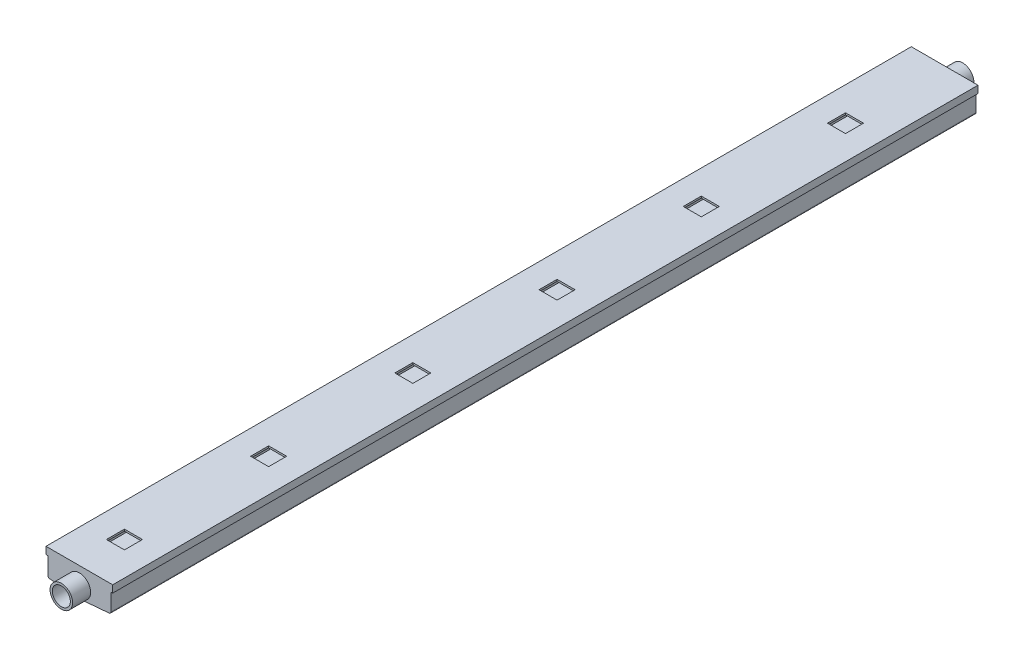
SolidWorks part; units mm, degrees
ref_plane "Front Plane" through (0, 0, 0) normal (0, 0, 1) x (1, 0, 0)
ref_plane "Top Plane" through (0, 0, 0) normal (0, 1, 0) x (1, 0, 0)
ref_plane "Right Plane" through (0, 0, 0) normal (1, 0, 0) x (0, 0, -1)
sketch "Sketch1" plane through (0, 0, 0) normal (0, 0, 1) x (1, 0, 0)
  line L2 (0, 0) -> (0, 34.29)
  line L3 (0, 34.29) -> (88.9, 34.29)
  line L4 (88.9, 0) -> (88.9, 34.29)
  line L5 (0, 0) -> (44.45, -3.81)
  line L6 (44.45, -3.81) -> (88.9, 0)
  point P5 (44.45, 34.29)
  dimension "D1" = 34.29
  dimension "D2" = 88.9
  dimension "D3" = 38.1
extrude "Boss-Extrude1" add sketch "Sketch1" along normal blind 1219.2
sketch "Sketch2" plane through (88.9, 0, 0) normal (1, 0, 0) x (0, 0, -1)
  line L0 (0, 0) -> (0, 34.29) construction
  line L1 (-1219.2, 34.29) -> (0, 34.29)
  line L2 (-1219.2, 34.29) -> (-1219.2, 26.67)
  line L3 (-1219.2, 26.67) -> (0, 26.67)
  line L4 (0, 34.29) -> (0, 26.67)
  dimension "D1" = 7.62
extrude "Boss-Extrude2" add sketch "Sketch2" along normal blind 2.54
sketch "Sketch3" plane through (0, 0, 0) normal (-1, 0, 0) x (0, 0, 1)
  line L0 (1219.2, 34.29) -> (1219.2, 0) construction
  line L1 (0, 34.29) -> (1219.2, 34.29)
  line L2 (0, 34.29) -> (0, 26.67)
  line L3 (0, 26.67) -> (1219.2, 26.67)
  line L4 (1219.2, 34.29) -> (1219.2, 26.67)
  dimension "D1" = 7.62
extrude "Boss-Extrude3" add sketch "Sketch3" along normal blind 2.54
sketch "Sketch4" plane through (0, 0, 0) normal (0, 0, -1) x (-1, 0, 0)
  circle A0 centre (-44.45, 12.065) radius 15.875
  circle A1 centre (-44.45, 12.065) radius 12.7
  dimension "D1" = 31.75
  dimension "D2" = 25.4
extrude "Boss-Extrude4" add sketch "Sketch4" along normal blind 25.4
sketch "Sketch5" plane through (0, 0, 0) normal (0, 0, -1) x (-1, 0, 0)
  circle A1 centre (-44.45, 12.065) radius 12.7
sketch "Sketch6" plane through (0, 0, 1219.2) normal (0, 0, 1) x (1, 0, 0)
  circle A0 centre (44.45, 12.065) radius 15.875
  circle A1 centre (44.45, 12.065) radius 12.7
  dimension "D1" = 31.75
extrude "Boss-Extrude5" add sketch "Sketch6" along normal blind 25.4
shell "Shell2" thickness 2.54 removed face at (44.45, 34.29, 609.6)
sketch "Sketch9" plane through (0, 34.29, 0) normal (0, 1, 0) x (1, 0, 0)
  line L1 (-2.54, -1219.2) -> (91.44, -1219.2)
  line L2 (-2.54, -1219.2) -> (-2.54, 0)
  line L3 (-2.54, 0) -> (91.44, 0)
  line L4 (91.44, -1219.2) -> (91.44, 0)
extrude "Boss-Extrude7" add sketch "Sketch9" along normal blind 2.54
fillet "Fillet1" radius 2.54 2 edges at (0, 0, 609.6) (88.9, 0, 609.6)
extrude "Cut-Extrude3" cut sketch "Sketch5" against normal up to next contours A1
sketch "Sketch11" plane through (0, 0, 1219.2) normal (0, 0, 1) x (1, 0, 0)
  circle A1 centre (44.45, 12.065) radius 12.7
extrude "Cut-Extrude4" cut sketch "Sketch11" against normal blind 2.54
sketch "Sketch12" plane through (0, 36.83, 0) normal (0, 1, 0) x (1, 0, 0)
  line L0 (44.45, -1219.2) -> (44.45, -1090.339) construction
  line L1 (-2.54, -1219.2) -> (91.44, -1219.2) construction
  line L3 (57.15, -1168.4) -> (31.75, -1168.4)
  line L4 (57.15, -1168.4) -> (57.15, -1143)
  line L5 (57.15, -1143) -> (31.75, -1143)
  line L6 (31.75, -1168.4) -> (31.75, -1143)
  line L7 (57.15, -1168.4) -> (31.75, -1143) construction
  line L8 (57.15, -1143) -> (31.75, -1168.4) construction
  point P4 (44.45, -1155.7)
  dimension "D1" = 25.4
  dimension "D2" = 50.8
extrude "Cut-Extrude5" cut sketch "Sketch12" against normal up to next
pattern_linear "LPattern1" count 6 spacing 203.2 along (0, 0, -1) of "Cut-Extrude5"
